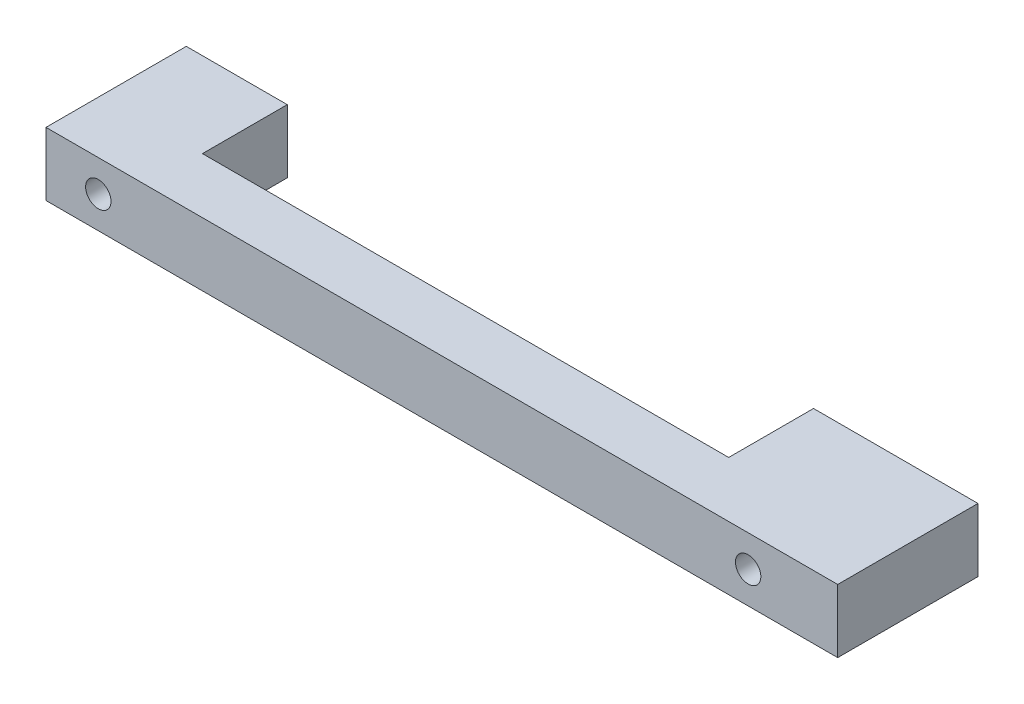
SolidWorks part; units mm, degrees
material "6061-T6 (SS)"
ref_plane "前视基准面" through (0, 0, 0) normal (0, 0, 1) x (1, 0, 0)
ref_plane "上视基准面" through (0, 0, 0) normal (0, 1, 0) x (1, 0, 0)
ref_plane "右视基准面" through (0, 0, 0) normal (1, 0, 0) x (0, 0, -1)
other "Configuration Table"
sketch "草图1" plane through (0, 0, 0) normal (0, 0, 1) x (1, 0, 0)
  line L1 (-0.3, 41.68) -> (49.65, 41.68)
  line L2 (-0.3, 41.68) -> (-0.3, 45.68)
  line L3 (-0.3, 45.68) -> (49.65, 45.68)
  line L4 (49.65, 41.68) -> (49.65, 45.68)
  dimension "D1" = 49.65
  dimension "D2" = 0.3
  dimension "D3" = 41.68
  dimension "D4" = 45.68
extrude "Rear_Interface_Plate" add sketch "草图1" along normal blind 8.8519
move or copy body "Stock_Z_Position" bodies to move or copy 106 copy no translate (0, 0, 2.2481) parameters "D1"=0, "D2"=0, "D3"=2.2481
sketch "草图2" plane through (0, 0, 11.1) normal (0, 0, 1) x (1, 0, 0)
  circle A0 centre (3, 43.68) radius 0.8
  circle A1 centre (44, 43.68) radius 0.8
  dimension "D1" = 1.6
  dimension "D2" = 3
  dimension "D3" = 44
  dimension "D4" = 43.68
extrude "Frame_2xD1p6_Through" cut sketch "草图2" against normal through all
cosmetic thread "Frame_M2_Through_Cosmetic_1" parameters "D2"=2
cosmetic thread "Frame_M2_Through_Cosmetic_2" parameters "D2"=2
sketch "草图3" plane through (0, 45.68, 0) normal (0, 1, 0) x (1, 0, 0)
  line L1 (6.07, -0.9) -> (39.273, -0.9)
  line L2 (6.07, -0.9) -> (6.07, -7.6)
  line L3 (6.07, -7.6) -> (39.273, -7.6)
  line L4 (39.273, -0.9) -> (39.273, -7.6)
  dimension "D1" = 6.07
  dimension "D2" = 39.273
  dimension "D3" = 0.9
  dimension "D4" = 7.6
extrude "Merged_Interface_Window_33p203x6p7" cut sketch "草图3" against normal blind 4
